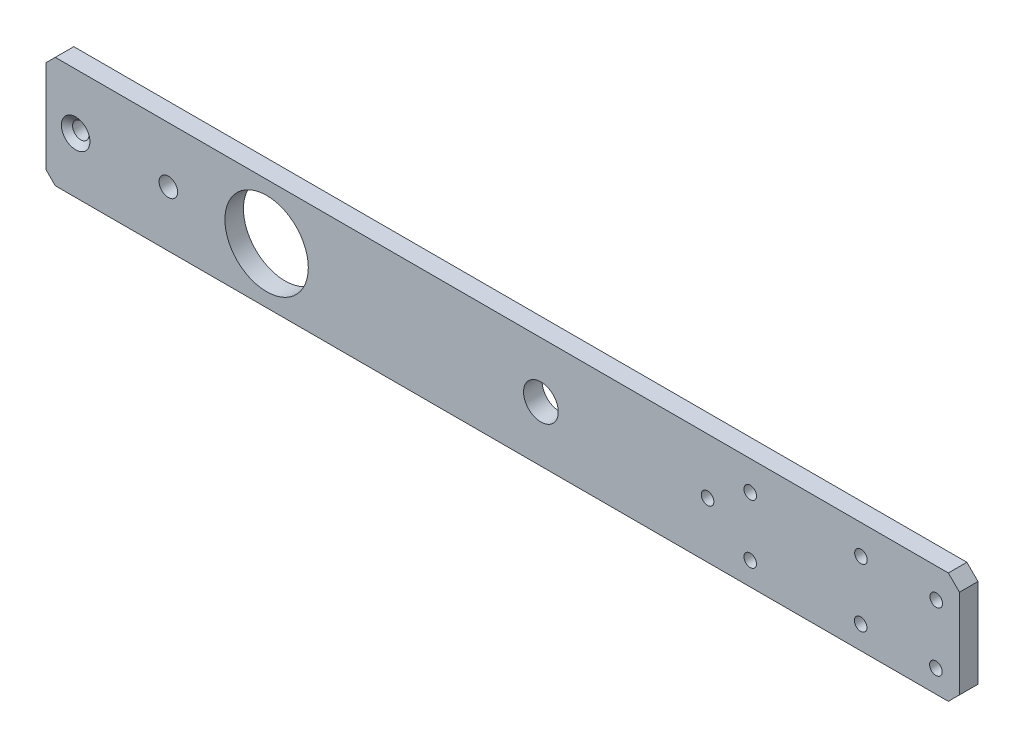
SolidWorks part; units mm, degrees
material "6061-T6 (SS)"
ref_plane "Front Plane" through (0, 0, 0) normal (0, 0, 1) x (1, 0, 0)
ref_plane "Top Plane" through (0, 0, 0) normal (0, 1, 0) x (1, 0, 0)
ref_plane "Right Plane" through (0, 0, 0) normal (1, 0, 0) x (0, 0, -1)
sketch "Sketch1" plane through (0, 0, 0) normal (0, 0, 1) x (1, 0, 0)
  line L0 (0, 19.05) -> (-28.575, 19.05)
  line L1 (0, -19.05) -> (247.2819, -19.05)
  line L2 (0, -19.05) -> (0, 19.05) construction
  line L3 (0, 19.05) -> (254, 19.05)
  line L5 (-28.575, 19.05) -> (-28.575, -19.05)
  line L6 (-28.575, -19.05) -> (0, -19.05)
  line L8 (254, 19.05) -> (247.2819, -19.05)
  circle A1 centre (0, 0) radius 14.2875
  dimension "D3" = 28.575
  dimension "D1" = 38.1
  dimension "D2" = 254
  dimension "D4" = 80
extrude "Boss-Extrude1" add sketch "Sketch1" along normal mid plane 6.35
hole_wizard "#6 Clearance Hole3" positions "Sketch8" profile "Sketch7" hole size "#6" standard "ANSI Inch" end condition through all
sketch "Sketch8" plane through (0, 0, 3.175) normal (0, 0, 1) x (1, 0, 0)
  line L9 (159.3222, 8.9914) -> (175.5726, 8.9914) construction
  line L12 (159.3222, -11.1439) -> (172.0222, -11.1439) construction
  line L13 (159.3222, 19.05) -> (159.3222, -19.05) construction
  line L26 (254, 19.05) -> (-28.575, 19.05) construction
  line L28 (-28.575, -19.05) -> (247.2819, -19.05) construction
  line L29 (159.3222, 0) -> (151.0672, 0) construction
  line L30 (165.6722, 8.9914) -> (165.6722, -11.1439) construction
  line L32 (177.3462, 19.05) -> (170.6012, -19.2024) construction
  point P0 (229.3887, 8.9238)
  point P3 (229.2824, -11.3468)
  point P6 (203.5032, -11.1439)
  point P9 (203.6088, 8.9914)
  point P12 (165.6722, 8.9914)
  point P15 (165.6722, -11.1439)
  point P18 (151.0672, 0)
  point P125 (0, 0)
  point P128 (0, 0)
  dimension "D1" = 6.35
  dimension "D2" = 8.255
sketch "Sketch7" plane through (229.3887, 8.9238, 3.175) normal (1, 0, 0) x (0, -1, 0)
  line L0 (0, 0) -> (0, 6.35)
  line L1 (0, 6.35) -> (2.1526, 6.35)
  line L2 (2.1526, 6.35) -> (2.1526, 0)
  line L5 (2.1526, 0) -> (0, 0)
  line L11 (0, -6.35) -> (0, 107.95) construction
  dimension "Thru Hole Dia." = 4.3053
  dimension "Thru Hole Depth" = 6.35
sketch "Sketch9" plane through (0, 0, 3.175) normal (0, 0, 1) x (1, 0, 0)
  line L0 (254, 19.05) -> (247.2819, -19.05)
  line L1 (254, 19.05) -> (237.3521, 19.05)
  line L2 (254, 19.05) -> (-28.575, 19.05) construction
  line L3 (237.3521, 19.05) -> (237.3521, -19.05)
  line L4 (-28.575, -19.05) -> (247.2819, -19.05) construction
  line L5 (237.3521, -19.05) -> (247.2819, -19.05)
  line L6 (243.8073, 17.5595) -> (237.0893, -20.5405) construction
extrude "Cut-Extrude1" cut sketch "Sketch9" against normal through all
chamfer "Chamfer1" distance 3.81 angle 45 4 edges at (-28.575, -19.05, 0) (-28.575, 19.05, 0) (237.3521, 19.05, 0) (237.3521, -19.05, 0)
sketch "Sketch10" plane through (0, 0, 3.175) normal (0, 0, 1) x (1, 0, 0)
  line L0 (-24.765, -19.05) -> (233.5421, -19.05) construction
  line L1 (-24.765, -19.05) -> (-75.565, -19.05)
  line L2 (-24.765, -19.05) -> (-24.765, 19.05)
  line L3 (-24.765, 19.05) -> (-75.565, 19.05)
  line L4 (-75.565, -19.05) -> (-75.565, 19.05)
  dimension "D1" = 50.8
extrude "Boss-Extrude2" add sketch "Sketch10" against normal through all
chamfer "Chamfer2" distance 3.175 angle 45 2 edges at (-75.565, -19.05, 0) (-75.565, 19.05, 0)
hole_wizard "CSK for #10 Flat Head Machine Screw (100)1" positions "Sketch11" profile "Sketch12" countersink size "#10" standard "ANSI Inch" end condition through all
sketch "Sketch11" plane through (0, 0, 3.175) normal (0, 0, 1) x (1, 0, 0)
  line L0 (0, 0) -> (-75.565, 0) construction
  line L1 (-75.565, 15.875) -> (-75.565, -15.875) construction
  point P0 (-65.405, 0)
  dimension "D1" = 10.16
sketch "Sketch12" plane through (-65.405, 0, 3.175) normal (1, 0, 0) x (0, -1, 0)
  line L0 (0, 0) -> (0, 6.35)
  line L1 (0, 6.35) -> (2.8067, 6.35)
  line L2 (2.8067, 6.35) -> (2.8067, 1.7477)
  line L3 (2.8067, 1.7477) -> (4.8895, 0)
  line L5 (4.8895, 0) -> (0, 0)
  line L6 (-2.8067, 1.7477) -> (-4.8895, 0) construction
  line L11 (0, -6.35) -> (0, 107.95) construction
  dimension "Thru Hole Dia." = 5.6134
  dimension "Thru Hole Depth" = 6.35
  dimension "Near C'Sink Dia." = 9.779
  dimension "Near C'Sink Angle" = 100
hole_wizard "1/4 (0.25) Diameter Hole1" positions "Sketch13" profile "Sketch14" hole size "1/4" standard "ANSI Inch" end condition through all
sketch "Sketch13" plane through (0, 0, 3.175) normal (0, 0, 1) x (1, 0, 0)
  line L0 (-75.565, 0) -> (-33.655, 0) construction
  line L1 (-75.565, 15.875) -> (-75.565, -15.875) construction
  circle A0 centre (-65.405, 0) radius 4.8895 construction
  point P0 (-33.655, 0)
  dimension "D1" = 31.75
sketch "Sketch14" plane through (-33.655, 0, 3.175) normal (1, 0, 0) x (0, -1, 0)
  line L0 (0, 0) -> (0, 6.35)
  line L1 (0, 6.35) -> (3.175, 6.35)
  line L2 (3.175, 6.35) -> (3.175, 0)
  line L5 (3.175, 0) -> (0, 0)
  line L11 (0, -6.35) -> (0, 107.95) construction
  dimension "Thru Hole Dia." = 6.35
  dimension "Thru Hole Depth" = 6.35
hole_wizard "CSK for #6 Flat Head Machine Screw (100)1" positions "Sketch15" profile "Sketch16" countersink size "#6" standard "ANSI Inch" end condition through all
sketch "Sketch15" plane through (0, 0, -3.175) normal (0, 0, -1) x (-1, 0, 0)
  point P0 (-151.0672, 0)
  point P3 (-165.6722, -11.1439)
  point P6 (-165.6722, 8.9914)
sketch "Sketch16" plane through (151.0672, 0, -3.175) normal (1, 0, 0) x (0, 1, 0)
  line L0 (0, 0) -> (0, 6.35)
  line L1 (0, 6.35) -> (2.1526, 6.35)
  line L2 (2.1526, 6.35) -> (2.1526, 1.1669)
  line L3 (2.1526, 1.1669) -> (3.5433, 0)
  line L5 (3.5433, 0) -> (0, 0)
  line L6 (-2.1526, 1.1669) -> (-3.5433, 0) construction
  line L11 (0, -6.35) -> (0, 107.95) construction
  dimension "Thru Hole Dia." = 4.3053
  dimension "Thru Hole Depth" = 6.35
  dimension "Near C'Sink Dia." = 7.0866
  dimension "Near C'Sink Angle" = 100
hole_wizard "15/32 (0.46875) Diameter Hole1" positions "Sketch17" profile "Sketch18" hole size "15/32" standard "ANSI Inch" end condition through all
sketch "Sketch17" plane through (0, 0, -3.175) normal (0, 0, -1) x (-1, 0, 0)
  line L0 (75.565, 15.875) -> (75.565, -15.875) construction
  point P0 (-93.9672, 0)
  dimension "D1" = 169.5322
sketch "Sketch18" plane through (93.9672, 0, -3.175) normal (1, 0, 0) x (0, 1, 0)
  line L0 (0, 0) -> (0, 6.35)
  line L1 (0, 6.35) -> (5.9531, 6.35)
  line L2 (5.9531, 6.35) -> (5.9531, 0)
  line L5 (5.9531, 0) -> (0, 0)
  line L11 (0, -6.35) -> (0, 107.95) construction
  dimension "Thru Hole Dia." = 11.9062
  dimension "Thru Hole Depth" = 6.35
